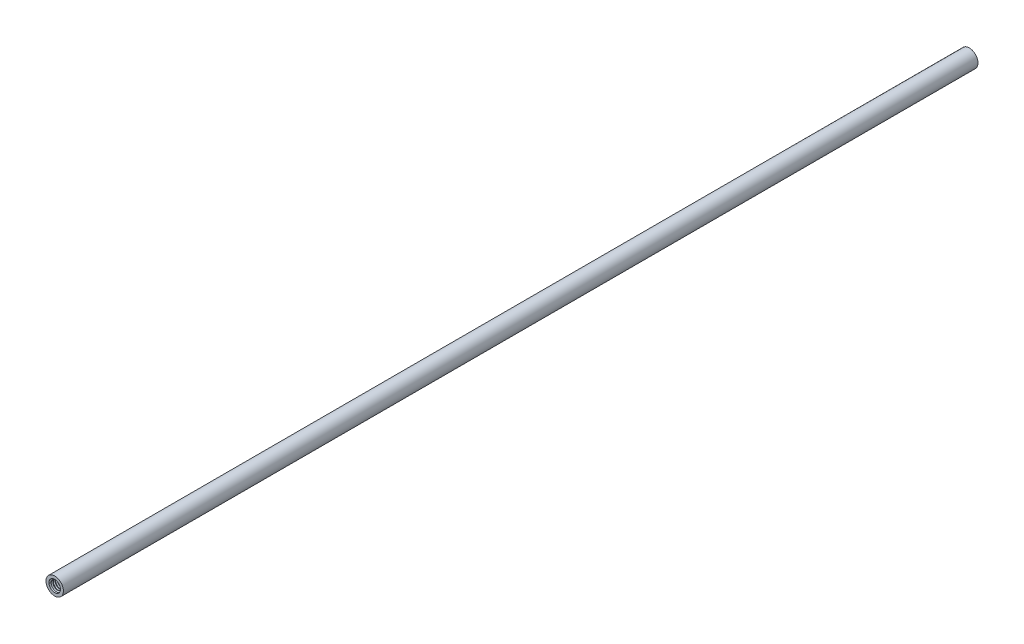
SolidWorks part; units mm, degrees
ref_plane "Front Plane" through (0, 0, 0) normal (0, 0, 1) x (1, 0, 0)
ref_plane "Top Plane" through (0, 0, 0) normal (0, 1, 0) x (1, 0, 0)
ref_plane "Right Plane" through (0, 0, 0) normal (1, 0, 0) x (0, 0, -1)
sketch "Sketch1" plane through (0, 0, 0) normal (0, 0, 1) x (1, 0, 0)
  circle A0 centre (0, 0) radius 6
  circle A1 centre (0, 0) radius 4
  dimension "D1" = 12
  dimension "D2" = 8
extrude "Boss-Extrude1" add sketch "Sketch1" along normal blind 630
thread "Thread1" pitch 1.5 method extrude profile "Thread Profile1" start angle 0, offset 0, length 25, pitch 1.5, diameter 8
ref_plane "Plane1" through (-4, 0, 630) normal (0, -1, 0) x (-1, 0, 0)
sketch "Thread Profile1" plane through (-4, 0, 630) normal (0, -1, 0) x (-1, 0, 0)
  line L0 (0, 0) -> (0, 1.5) construction
  line L11 (0, 0) -> (0, 1.3125)
  line L12 (0, 1.3125) -> (-0.8119, 0.8437)
  line L13 (-0.8119, 0.8437) -> (-0.8119, 0.4687)
  line L15 (-0.8119, 0.4687) -> (0, 0)
  line L17 (-0.8119, 0.6562) -> (0, 0.6562) construction
  point P2 (0, 0)
  dimension "Pitch" = 1.5
  dimension "Profile_Angle" = 60
  dimension "Profile_Land" = 0.375
  dimension "Profile_Height" = 0.8119
thread "Thread2" pitch 1.5 method extrude profile "Thread Profile2" start angle 0, offset 0, length 25, pitch 1.5, diameter 8
ref_plane "Plane2" through (4, 0, 0) normal (0, -1, 0) x (1, 0, 0)
sketch "Thread Profile2" plane through (4, 0, 0) normal (0, -1, 0) x (1, 0, 0)
  line L0 (0, 0) -> (0, 1.5) construction
  line L11 (0, 0) -> (0, 1.3125)
  line L12 (0, 1.3125) -> (-0.8119, 0.8437)
  line L13 (-0.8119, 0.8437) -> (-0.8119, 0.4687)
  line L15 (-0.8119, 0.4687) -> (0, 0)
  line L17 (-0.8119, 0.6562) -> (0, 0.6562) construction
  point P2 (0, 0)
  dimension "Pitch" = 1.5
  dimension "Profile_Angle" = 60
  dimension "Profile_Land" = 0.375
  dimension "Profile_Height" = 0.8119
